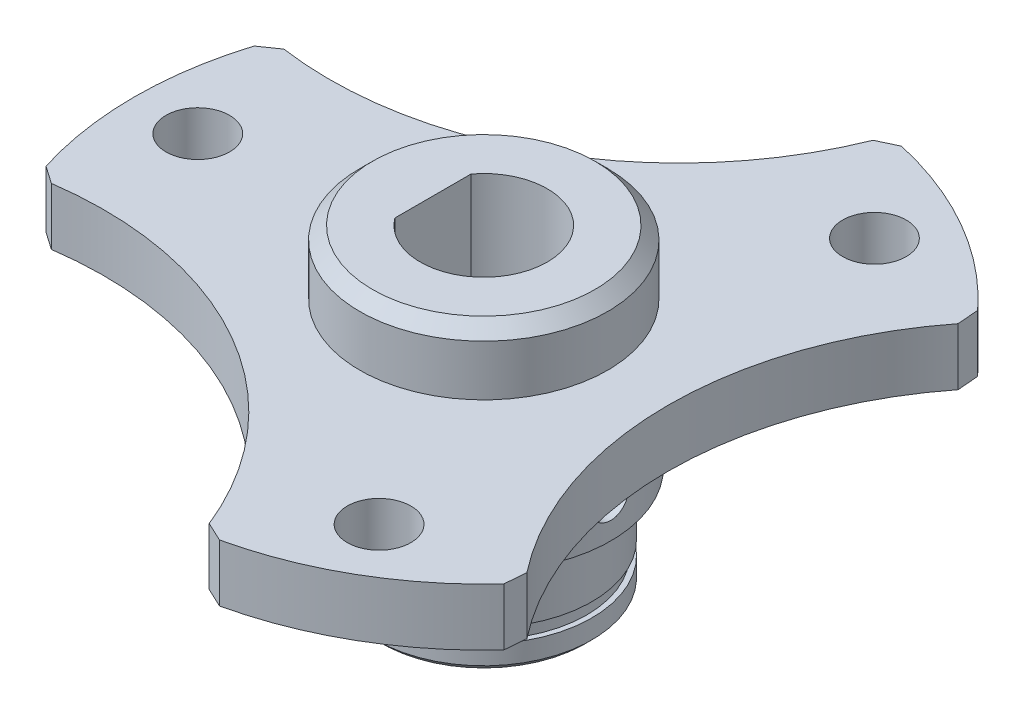
SolidWorks part; units mm, degrees
material "6061 合金"
ref_plane "前视基准面" through (0, 0, 0) normal (0, 0, 1) x (1, 0, 0)
ref_plane "上视基准面" through (0, 0, 0) normal (0, 1, 0) x (1, 0, 0)
ref_plane "右视基准面" through (0, 0, 0) normal (1, 0, 0) x (0, 0, -1)
sketch "草图1" plane through (0, 0, 0) normal (0, 1, 0) x (1, 0, 0)
  circle A0 centre (0, 0) radius 27.5
  dimension "D1" = 55
extrude "凸台-拉伸1" add sketch "草图1" along normal blind 4.5
sketch "草图2" plane through (0, 4.5, 0) normal (0, 1, 0) x (1, 0, 0)
  circle A0 centre (0, 0) radius 9.75
  dimension "D1" = 19.5
extrude "凸台-拉伸2" add sketch "草图2" along normal blind 30.8
sketch "草图4" plane through (0, 35.3, 0) normal (0, 1, 0) x (1, 0, 0)
  line L0 (-4, 3) -> (-4, -3)
  arc A0 (-4, -3) -> (-4, 3) centre (0, 0) ccw
  dimension "D1" = 10
  dimension "D2" = 4
extrude "切除-拉伸1" cut sketch "草图4" against normal blind 28
sketch "草图5" plane through (0, 0, 0) normal (0, -1, 0) x (1, 0, 0)
  circle A0 centre (0, 0) radius 10
  dimension "D1" = 20
extrude "凸台-拉伸3" add sketch "草图5" along normal blind 7
sketch "草图6" plane through (0, -7, 0) normal (0, -1, 0) x (1, 0, 0)
  circle A0 centre (0, 0) radius 8.5
  dimension "D1" = 17
extrude "凸台-拉伸4" add sketch "草图6" along normal blind 8
sketch "草图11" plane through (0, 4.5, 0) normal (0, 1, 0) x (1, 0, 0)
  line L0 (0, 0) -> (-49.7158, 0) construction
  circle A0 centre (-22.5, 0) radius 2.5
  dimension "D1" = 22.5
  dimension "D2" = 5
extrude "切除-拉伸3" cut sketch "草图11" against normal through all
ref_axis "基准轴1" through (0, 20.9929, 0) along (0, -1, 0)
pattern_circular "阵列(圆周)1" count 6 over 360 about axis through (0, 20.9929, 0) along (0, -1, 0) of "切除-拉伸3"
sketch "草图12" plane through (0, 35.3, 0) normal (0, 1, 0) x (1, 0, 0)
  circle A0 centre (0, 0) radius 13.0081
extrude "切除-拉伸4" cut sketch "草图12" against normal offset from surface (25.8 mm away) 5 up to face at (-9.0849, 4.5, 20.7356)
chamfer "倒角2" distance 1 angle 45 1 edges at (0, 9.5, 9.75)
sketch "草图13" plane through (0, 0, 0) normal (0, 0, 1) x (1, 0, 0)
  line L0 (-8.5, -11.9) -> (-8.1, -11.9)
  line L1 (-8.5, -7) -> (-8.5, -12) construction
  line L2 (-8.1, -11.9) -> (-8.1, -13)
  line L3 (-8.1, -13) -> (-8.5, -13)
  line L4 (-8.5, -13) -> (-8.5, -11.9)
  line L5 (-8.5, -15) -> (8.5, -15) construction
  dimension "D1" = 2
  dimension "D2" = 1.1
  dimension "D3" = 0.4
revolve "切除-旋转1" cut sketch "草图13" angle 360 about axis through (0, 20.9929, 0) along (0, -1, 0)
chamfer "倒角3" distance 0.5 angle 45 1 edges at (0, -15, -8.5)
sketch "草图14" plane through (0, -15, 0) normal (0, -1, 0) x (1, 0, 0)
  line L0 (-4, -3) -> (-4, 3)
  arc A0 (-4, -3) -> (-4, 3) centre (0, 0) ccw
  dimension "D1" = 10
  dimension "D2" = 4
extrude "切除-拉伸5" cut sketch "草图14" against normal through all
sketch "草图15" plane through (0, 0, 0) normal (1, 0, 0) x (0, 0, -1)
  line L0 (0, 20.9929) -> (0, -26.1109) construction
  line L2 (-8.5, -7) -> (8.5, -7) construction
  circle A0 centre (0, -4) radius 1.6
  dimension "D1" = 3.2
  dimension "D2" = 3
extrude "切除-拉伸6" cut sketch "草图15" along normal blind 25
hole_wizard "M3 螺纹孔1" positions "草图17" profile "草图16" tap size "M3" standard "GB" end condition through all
sketch "草图17" plane through (-4, 0, 0) normal (1, 0, 0) x (0, 0, -1)
  point P0 (0, -4)
sketch "草图16" plane through (-4, -4, 0) normal (0, 1, 0) x (0, 0, -1)
  line L0 (0, 0) -> (0, 23.5)
  line L1 (0, 23.5) -> (1.25, 23.5)
  line L2 (1.25, 23.5) -> (1.25, 0)
  line L5 (1.25, 0) -> (0, 0)
  line L11 (0, -6.35) -> (0, 107.95) construction
  dimension "通孔螺纹孔钻头直径" = 2.5
  dimension "通孔螺纹孔钻头深度" = 23.5
cosmetic thread "孔螺蚊线1" parameters "D2"=3
sketch "草图18" plane through (0, 4.5, 0) normal (0, 1, 0) x (1, 0, 0)
  circle A0 centre (42, 0) radius 27.5
  circle A1 centre (0, 0) radius 27.5 construction
  dimension "D1" = 55
  dimension "D2" = 42
extrude "切除-拉伸7" cut sketch "草图18" against normal through all
pattern_circular "阵列(圆周)2" count 3 over 240 about axis through (0, -7, 0) along (0, 1, 0) of "切除-拉伸7"
chamfer "倒角4" distance 1 angle 45 6 edges at (-25.8765, 2.25, -9.3089) (-25.8765, 2.25, 9.3089) (4.8765, 2.25, 27.0642) (21, 2.25, 17.7553) (21, 2.25, -17.7553) (4.8765, 2.25, -27.0642) first distance on face at (-8.875, 2.25, -15.372) first distance on face at (-8.875, 2.25, 15.372) first distance on face at (17.75, 2.25, 0)
sketch "草图19" plane through (0, -15, 0) normal (0, -1, 0) x (1, 0, 0)
  circle A0 centre (0, 0) radius 5
  dimension "D1" = 10
extrude "切除-拉伸8" cut sketch "草图19" against normal blind 1
